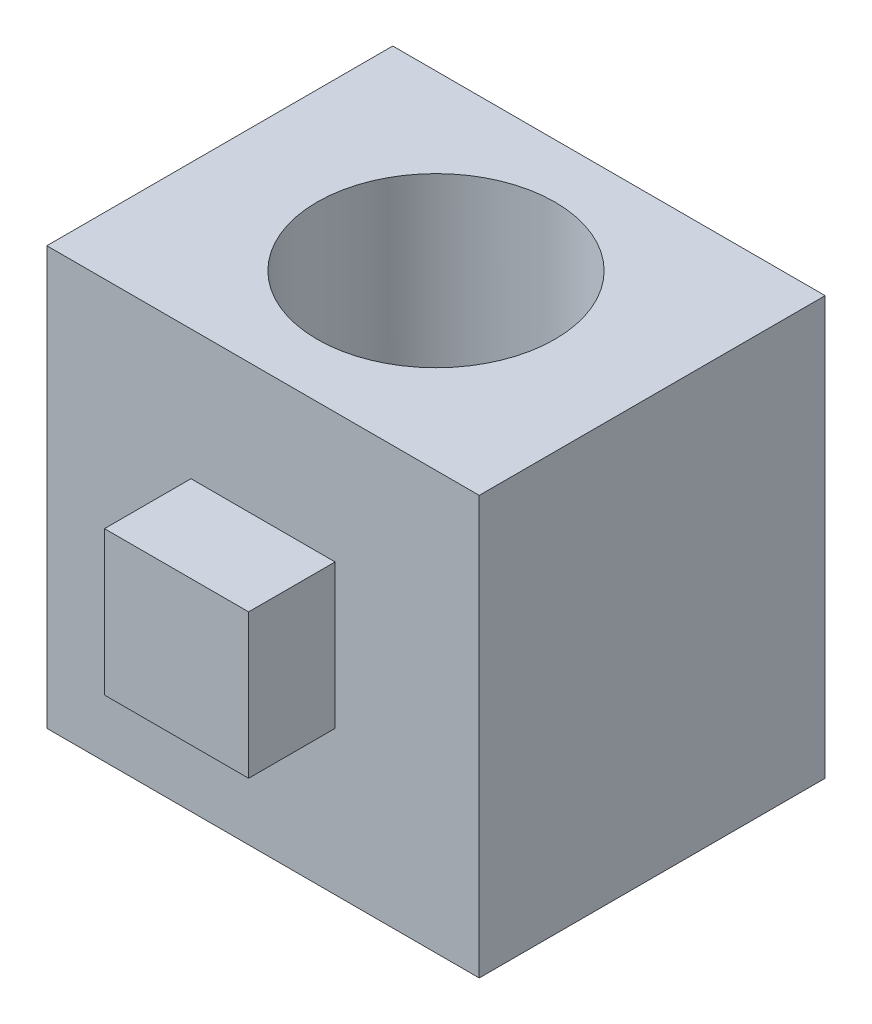
SolidWorks part; units mm, degrees
material "Gray Cast Iron"
ref_plane "Front Plane" through (0, 0, 0) normal (0, 0, 1) x (1, 0, 0)
ref_plane "Top Plane" through (0, 0, 0) normal (0, 1, 0) x (1, 0, 0)
ref_plane "Right Plane" through (0, 0, 0) normal (1, 0, 0) x (0, 0, -1)
sketch "Sketch1" plane through (0, 0, 0) normal (0, 0, 1) x (1, 0, 0)
  line L0 (-15, 0) -> (15, 0)
  line L1 (15, 0) -> (15, 29)
  line L2 (15, 29) -> (-15, 29)
  line L3 (-15, 29) -> (-15, 0)
extrude "Boss-Extrude1" add sketch "Sketch1" along normal mid plane 24
sketch "Sketch2" plane through (0, 0, 0) normal (0, 1, 0) x (1, 0, 0)
  circle A0 centre (0, 0) radius 8.25
  dimension "D1" = 16.5
extrude "Cut-Extrude1" cut sketch "Sketch2" against normal mid plane 68
sketch "Sketch3" plane through (0, 0, 0) normal (0, 0, 1) x (1, 0, 0)
  line L0 (-5, 10) -> (5, 10)
  line L1 (5, 10) -> (5, 20)
  line L2 (5, 20) -> (-5, 20)
  line L3 (-5, 20) -> (-5, 10)
extrude "Boss-Extrude2" add sketch "Sketch3" along normal blind 6 from offset 12
